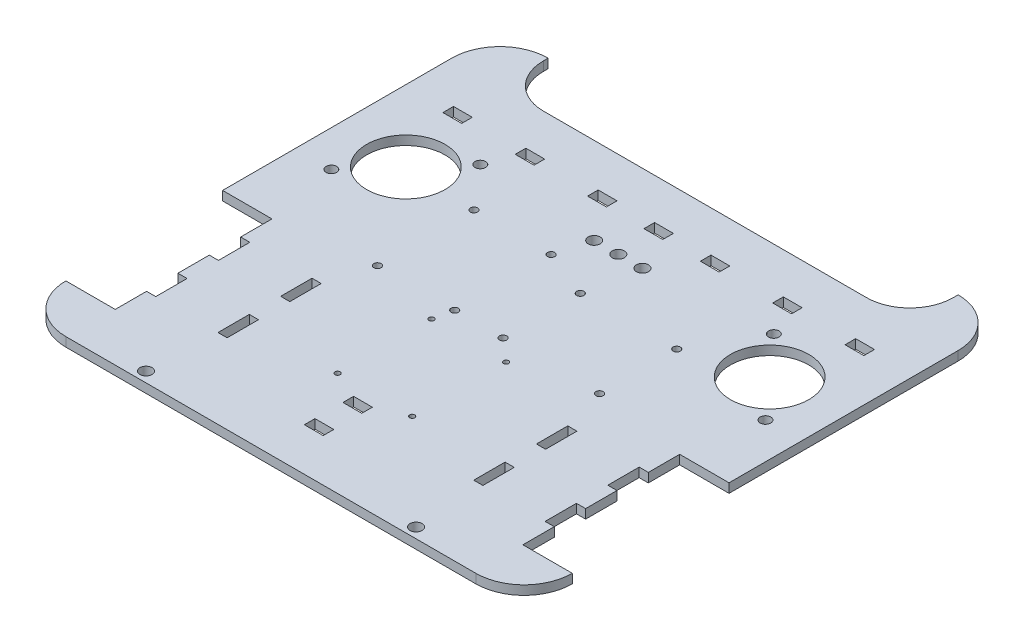
SolidWorks part; units mm, degrees
ref_plane "Front Plane" through (0, 0, 0) normal (0, 0, 1) x (1, 0, 0)
ref_plane "Top Plane" through (0, 0, 0) normal (0, 1, 0) x (1, 0, 0)
ref_plane "Right Plane" through (0, 0, 0) normal (1, 0, 0) x (0, 0, -1)
sketch "Sketch1" plane through (0, 0, 0) normal (0, 1, 0) x (1, 0, 0)
  line L1 (-133.35, 127) -> (133.35, 127)
  line L2 (-133.35, 127) -> (-133.35, -127)
  line L3 (-133.35, -127) -> (133.35, -127)
  line L4 (133.35, 127) -> (133.35, -127)
  line L5 (-133.35, 127) -> (133.35, -127) construction
  line L6 (-133.35, -127) -> (133.35, 127) construction
  point P0 (0, 0)
  dimension "D1" = 266.7
  dimension "D2" = 254
extrude "Boss-Extrude1" add sketch "Sketch1" along normal blind 4.826
sketch "Sketch2" plane through (0, 4.826, 0) normal (0, 1, 0) x (1, 0, 0)
  line L0 (-133.35, 127) -> (-133.35, -127) construction
  line L1 (-133.35, -19.05) -> (-107.35, -19.05)
  line L2 (-133.35, -19.05) -> (-133.35, -101.6)
  line L3 (-133.35, -101.6) -> (-107.35, -101.6)
  line L4 (-107.35, -19.05) -> (-107.35, -101.6)
  line L5 (133.35, -127) -> (133.35, 127) construction
  line L6 (133.35, -19.05) -> (107.35, -19.05)
  line L7 (133.35, -19.05) -> (133.35, -101.6)
  line L8 (133.35, -101.6) -> (107.35, -101.6)
  line L9 (107.35, -19.05) -> (107.35, -101.6)
  line L10 (-133.35, -127) -> (133.35, -127) construction
  dimension "D1" = 25.4
  dimension "D2" = 25.4
  dimension "D3" = 82.55
  dimension "D4" = 82.55
  dimension "D5" = 26
  dimension "D6" = 26
extrude "Cut-Extrude1" cut sketch "Sketch2" against normal blind 4.826
sketch "Sketch4" plane through (0, 4.826, 0) normal (0, 1, 0) x (1, 0, 0)
  line L0 (0, -127) -> (0, 127) construction
  line L1 (-133.35, -127) -> (133.35, -127) construction
  line L2 (133.35, 127) -> (-133.35, 127) construction
  line L3 (-133.35, 101.6) -> (-107.95, 101.6) construction
  line L4 (-133.35, 127) -> (-133.35, -19.05) construction
  line L5 (-107.95, 101.6) -> (-107.95, 127) construction
  line L6 (-133.35, 101.6) -> (-133.35, 127)
  line L7 (-133.35, 127) -> (-107.95, 127)
  line L8 (133.35, 101.6) -> (133.35, 127)
  line L9 (133.35, 127) -> (107.95, 127)
  arc A0 (-133.35, 101.6) -> (-107.95, 127) centre (-107.95, 101.6) cw
  arc A1 (133.35, 101.6) -> (107.95, 127) centre (107.95, 101.6) ccw
extrude "Cut-Extrude3" cut sketch "Sketch4" against normal blind 4.826
sketch "Sketch7" plane through (0, 4.826, 0) normal (0, 1, 0) x (1, 0, 0)
  line L0 (0, -127) -> (0, 127) construction
  line L1 (-133.35, -127) -> (133.35, -127) construction
  line L2 (107.95, 127) -> (-107.95, 127) construction
  line L3 (107.95, 101.6) -> (107.95, 127)
  line L4 (107.95, 101.6) -> (-107.95, 101.6)
  line L5 (0, 101.6) -> (0, 127)
  line L6 (107.95, 127) -> (-107.95, 127)
  line L7 (-107.95, 101.6) -> (-107.95, 127)
  line M6 (107.95, 127) -> (-107.95, 127)
  dimension "D2" = 107.95
extrude "Cut-Extrude5" cut sketch "Sketch7" against normal blind 4.826 contours L7 L4 L5 M6 | L5 L4 L3 M6 region at (53.975, 4.826, -114.3) region at (-53.975, 4.826, -114.3)
fillet "Fillet9" radius 22.86 1 edges at (-107.95, 2.413, -101.6) type face fillet first side face at (0, 2.413, -101.6) second side face at (-107.95, 2.413, -114.3)
fillet "Fillet10" radius 22.86 1 edges at (107.95, 2.413, -101.6) type face fillet first side face at (11.43, 2.413, -101.6) second side face at (107.95, 2.413, -114.3)
sketch "Sketch8" plane through (0, 4.826, 0) normal (0, 1, 0) x (1, 0, 0)
  line L0 (-133.35, -101.6) -> (-107.95, -101.6) construction
  line L1 (-107.95, -101.6) -> (-107.95, -127) construction
  line L2 (-133.35, -127) -> (133.35, -127) construction
  line L3 (-133.35, -101.6) -> (-133.35, -127)
  line L4 (-133.35, -127) -> (-107.95, -127)
  line L5 (0, -127) -> (0, 101.6) construction
  line L6 (85.09, 101.6) -> (-85.09, 101.6) construction
  line L7 (133.35, -127) -> (107.95, -127)
  line L8 (133.35, -101.6) -> (133.35, -127)
  arc A0 (-133.35, -101.6) -> (-107.95, -127) centre (-107.95, -101.6) ccw
  arc A1 (133.35, -101.6) -> (107.95, -127) centre (107.95, -101.6) cw
extrude "Cut-Extrude6" cut sketch "Sketch8" against normal blind 4.826
sketch "Sketch9" plane through (0, 4.826, 0) normal (0, 1, 0) x (1, 0, 0)
  line L0 (0, 0) -> (133.35, 0) construction
  line L1 (133.35, -19.05) -> (133.35, 101.6) construction
  line L2 (0, 0) -> (-133.35, 0) construction
  line L3 (-133.35, 101.6) -> (-133.35, -19.05) construction
  line L4 (0, 101.6) -> (0, -127) construction
  line L5 (85.09, 101.6) -> (-85.09, 101.6) construction
  line L6 (-107.95, -127) -> (107.95, -127) construction
  circle A2 centre (-71.12, -121.629) radius 3.175
  circle A3 centre (71.12, -121.629) radius 3.175
  dimension "D3" = 6.35
  dimension "D6" = 71.12
extrude "Cut-Extrude7" cut sketch "Sketch9" against normal blind 4.826
sketch "Sketch10" plane through (0, 4.826, 0) normal (0, 1, 0) x (1, 0, 0)
  line L0 (-107.35, -101.6) -> (-107.35, -19.05) construction
  line L1 (-107.35, -35.56) -> (-102.524, -35.56)
  line L2 (-107.35, -35.56) -> (-107.35, -52.07)
  line L3 (-107.35, -52.07) -> (-102.524, -52.07)
  line L4 (-102.524, -35.56) -> (-102.524, -52.07)
  line L5 (107.35, -19.05) -> (107.35, -101.6) construction
  line L6 (-107.35, -68.58) -> (-102.524, -68.58)
  line L7 (-107.35, -68.58) -> (-107.35, -85.09)
  line L8 (-107.35, -85.09) -> (-102.524, -85.09)
  line L9 (-102.524, -68.58) -> (-102.524, -85.09)
  line L10 (107.35, -35.56) -> (102.524, -35.56)
  line L11 (107.35, -35.56) -> (107.35, -52.07)
  line L12 (107.35, -52.07) -> (102.524, -52.07)
  line L13 (102.524, -35.56) -> (102.524, -52.07)
  line L14 (-107.35, -19.05) -> (-102.524, -19.05) construction
  line L15 (107.35, -68.58) -> (102.524, -68.58)
  line L16 (107.35, -68.58) -> (107.35, -85.09)
  line L17 (107.35, -85.09) -> (102.524, -85.09)
  line L18 (102.524, -68.58) -> (102.524, -85.09)
  line L19 (-102.524, -19.05) -> (-102.524, -35.56) construction
  line L20 (-102.524, -52.07) -> (-102.524, -68.58) construction
  line L21 (-102.524, -68.58) -> (-83.474, -80.9089) construction
  line L22 (-107.35, -101.6) -> (-102.524, -101.6)
  line L23 (-102.524, -101.6) -> (-102.524, -85.09)
  line L24 (-102.524, -85.09) -> (-83.474, -98.2941)
  line L25 (107.35, -101.6) -> (102.524, -101.6)
  line L26 (102.524, -101.6) -> (102.524, -85.09)
  line L27 (102.524, -68.58) -> (102.524, -52.07)
  line L28 (107.35, -19.05) -> (102.524, -19.05)
  line L29 (102.524, -19.05) -> (102.524, -35.56)
  line M19 (107.35, -101.6) -> (107.35, -19.05)
  line M35 (-107.35, -19.05) -> (-107.35, -101.6)
  dimension "D1" = 4.826
  dimension "D2" = 4.826
extrude "Cut-Extrude8" cut sketch "Sketch10" against normal through all contours L9 L6 L8 M35 | L10 L13 L12 M19 | L15 L18 L17 M19 | L2 L3 L4 L1 region at (-104.937, 4.826, 76.835) region at (104.937, 4.826, 43.815) region at (104.937, 4.826, 76.835)
sketch "Sketch12" plane through (0, 0, 0) normal (0, -1, 0) x (1, 0, 0)
  line L0 (-64.932, 68.58) -> (-64.932, 85.09) construction
  line L1 (-64.932, 68.58) -> (-69.758, 68.58) construction
  line L2 (-69.758, 68.58) -> (-69.758, 85.09) construction
  line L3 (-64.932, 85.09) -> (-69.758, 85.09) construction
  line L4 (-64.932, 52.07) -> (-69.758, 52.07) construction
  line L5 (-64.932, 35.56) -> (-64.932, 52.07) construction
  line L6 (-64.932, 35.56) -> (-69.758, 35.56) construction
  line L7 (-69.758, 35.56) -> (-69.758, 52.07) construction
  line L8 (-64.932, 68.58) -> (-64.932, 85.09)
  line L9 (-64.932, 68.58) -> (-69.758, 68.58)
  line L10 (-69.758, 68.58) -> (-69.758, 85.09)
  line L11 (-64.932, 85.09) -> (-69.758, 85.09)
  line L12 (-64.932, 52.07) -> (-69.758, 52.07)
  line L13 (-64.932, 35.56) -> (-64.932, 52.07)
  line L14 (-64.932, 35.56) -> (-69.758, 35.56)
  line L15 (-69.758, 35.56) -> (-69.758, 52.07)
extrude "Cut-Extrude9" cut sketch "Sketch12" against normal through all
sketch "Sketch13" plane through (0, 4.826, 0) normal (0, 1, 0) x (1, 0, 0)
  line L0 (69.758, -68.58) -> (69.758, -85.09) construction
  line L1 (69.758, -68.58) -> (64.932, -68.58) construction
  line L2 (64.932, -68.58) -> (64.932, -85.09) construction
  line L3 (69.758, -85.09) -> (64.932, -85.09) construction
  line L4 (69.758, -52.07) -> (64.932, -52.07) construction
  line L5 (69.758, -35.56) -> (69.758, -52.07) construction
  line L6 (69.758, -35.56) -> (64.932, -35.56) construction
  line L7 (64.932, -35.56) -> (64.932, -52.07) construction
  line L8 (69.758, -68.58) -> (69.758, -85.09)
  line L9 (69.758, -68.58) -> (64.932, -68.58)
  line L10 (64.932, -68.58) -> (64.932, -85.09)
  line L11 (69.758, -85.09) -> (64.932, -85.09)
  line L12 (69.758, -52.07) -> (64.932, -52.07)
  line L13 (69.758, -35.56) -> (69.758, -52.07)
  line L14 (69.758, -35.56) -> (64.932, -35.56)
  line L15 (64.932, -35.56) -> (64.932, -52.07)
extrude "Cut-Extrude10" cut sketch "Sketch13" against normal through all
sketch "Sketch14" plane through (0, 4.826, 0) normal (0, 1, 0) x (1, 0, 0)
  line L0 (-133.35, -19.05) -> (133.35, -19.05) construction
  line L1 (0, -19.05) -> (0, -127) construction
  line L2 (-107.95, -127) -> (107.95, -127) construction
  line L3 (-22.86, -19.05) -> (-22.86, -127) construction
  line L4 (22.86, -19.05) -> (22.86, -127) construction
  dimension "D1" = 22.86
sketch "Sketch15" plane through (0, 4.826, 0) normal (0, 1, 0) x (1, 0, 0)
  circle A0 centre (19.5961, -22.7308) radius 1.3462 construction
  circle A1 centre (-19.6723, -22.7308) radius 1.3462 construction
  circle A2 centre (-19.6723, -72.1636) radius 1.3462 construction
  circle A3 centre (19.5961, -72.1636) radius 1.3462 construction
  circle A4 centre (19.5961, -22.7308) radius 1.3462
  circle A5 centre (-19.6723, -22.7308) radius 1.3462
  circle A6 centre (-19.6723, -72.1636) radius 1.3462
  circle A7 centre (19.5961, -72.1636) radius 1.3462
extrude "Cut-Extrude11" cut sketch "Sketch15" against normal through all
sketch "Sketch16" plane through (0, 4.826, 0) normal (0, 1, 0) x (1, 0, 0)
  line L0 (0, 101.6) -> (0, -127) construction
  line L1 (85.09, 101.6) -> (-85.09, 101.6) construction
  circle A0 centre (77.2939, 60.6102) radius 2.7781 construction
  circle A1 centre (114.3, 19.1646) radius 2.7781 construction
  circle A2 centre (95.7969, 39.8874) radius 20.6375 construction
  circle A3 centre (77.2939, 60.6102) radius 2.7781
  circle A4 centre (114.3, 19.1646) radius 2.7781
  circle A5 centre (95.7969, 39.8874) radius 20.6375
  circle A6 centre (-95.7969, 39.8874) radius 20.6375
  circle A7 centre (-77.2939, 60.6102) radius 2.7781
  circle A8 centre (-114.3, 19.1646) radius 2.7781
extrude "Cut-Extrude12" cut sketch "Sketch16" against normal through all
sketch "Sketch17" plane through (0, 4.826, 0) normal (0, 1, 0) x (1, 0, 0)
  line L0 (-62.8429, 80.0388) -> (-62.8429, 74.4508)
  line L1 (-110.8489, 80.0388) -> (-100.9429, 80.0388)
  line L2 (-110.8489, 80.0388) -> (-110.8489, 74.4508)
  line L3 (-110.8489, 74.4508) -> (-100.9429, 74.4508)
  line L4 (-100.9429, 80.0388) -> (-100.9429, 74.4508)
  line L9 (-72.7489, 80.0388) -> (-62.8429, 80.0388)
  line L10 (-72.7489, 80.0388) -> (-72.7489, 74.4508)
  line L11 (-72.7489, 74.4508) -> (-62.8429, 74.4508)
  line L12 (-24.7429, 80.0388) -> (-24.7429, 74.4508)
  line L13 (-34.6489, 80.0388) -> (-24.7429, 80.0388)
  line L14 (-34.6489, 80.0388) -> (-34.6489, 74.4508)
  line L15 (-34.6489, 74.4508) -> (-24.7429, 74.4508)
  line L16 (-133.35, 101.6) -> (-133.35, -19.05) construction
  line L17 (0, 101.6) -> (0, -127)
  line L18 (85.09, 101.6) -> (-85.09, 101.6) construction
  line L19 (-100.9429, 74.4508) -> (-78.3377, 74.4508) construction
  line L20 (24.7429, 80.0388) -> (24.7429, 74.4508)
  line L21 (34.6489, 80.0388) -> (24.7429, 80.0388)
  line L22 (34.6489, 80.0388) -> (34.6489, 74.4508)
  line L23 (34.6489, 74.4508) -> (24.7429, 74.4508)
  line L24 (62.8429, 80.0388) -> (62.8429, 74.4508)
  line L25 (72.7489, 74.4508) -> (62.8429, 74.4508)
  line L26 (72.7489, 80.0388) -> (72.7489, 74.4508)
  line L27 (72.7489, 80.0388) -> (62.8429, 80.0388)
  line L28 (110.8489, 80.0388) -> (100.9429, 80.0388)
  line L29 (110.8489, 80.0388) -> (110.8489, 74.4508)
  line L30 (110.8489, 74.4508) -> (100.9429, 74.4508)
  line L31 (100.9429, 80.0388) -> (100.9429, 74.4508)
  line L36 (4.953, 74.4508) -> (4.953, 80.0388)
  line L37 (4.953, 74.4508) -> (-4.953, 74.4508)
  line L38 (4.953, 80.0388) -> (-4.953, 80.0388)
  line L39 (-4.953, 74.4508) -> (-4.953, 80.0388)
  line L40 (4.953, 74.4508) -> (-4.953, 80.0388) construction
  line L41 (4.953, 80.0388) -> (-4.953, 74.4508) construction
  point P42 (0, 77.2448)
  dimension "D1" = 9.906
  dimension "D2" = 5.588
  dimension "D6" = 3
  dimension "D7" = 22.5011
  dimension "D8" = 9.906
  dimension "D9" = 0
extrude "Cut-Extrude13" cut sketch "Sketch17" against normal through all contours L28 L31 L30 L29 | L26 L27 L24 L25 | L23 L22 L21 L20 | L36 L38 L17 L37 | L39 L37 L17 L38 | L14 L15 L12 L13 | L10 L11 L0 L9 | L4 L1 L2 L3 region at (-67.7959, 4.826, -77.2448) region at (-105.8959, 4.826, -77.2448) region at (-29.6959, 4.826, -77.2448) region at (2.4765, 4.826, -77.2448) region at (-2.4765, 4.826, -77.2448) region at (29.6959, 4.826, -77.2448) region at (67.7959, 4.826, -77.2448) region at (105.8959, 4.826, -77.2448)
sketch "Sketch18" plane through (0, 4.826, 0) normal (0, 1, 0) x (1, 0, 0)
  line L0 (-4.953, -104.394) -> (4.953, -104.394)
  line L1 (-4.953, -104.394) -> (-4.953, -98.806)
  line L2 (4.953, -104.394) -> (4.953, -98.806)
  line L3 (-4.953, -98.806) -> (4.953, -98.806)
  line L4 (-4.953, -104.394) -> (4.953, -98.806) construction
  line L5 (4.953, -104.394) -> (-4.953, -98.806) construction
  line L6 (0, -19.05) -> (0, -127) construction
  line L7 (-4.953, -84.074) -> (4.953, -84.074)
  line L8 (-4.953, -84.074) -> (-4.953, -78.486)
  line L9 (4.953, -84.074) -> (4.953, -78.486)
  line L10 (-4.953, -78.486) -> (4.953, -78.486)
  line L11 (-4.953, -84.074) -> (4.953, -78.486) construction
  line L12 (4.953, -84.074) -> (-4.953, -78.486) construction
  point P1 (0, -101.6)
  point P10 (0, -81.28)
  dimension "D1" = 9.906
  dimension "D2" = 5.588
  dimension "D3" = 0
  dimension "D4" = 25.4
  dimension "D5" = 2
extrude "Cut-Extrude14" cut sketch "Sketch18" against normal through all
sketch "Sketch19" plane through (0, 4.826, 0) normal (0, 1, 0) x (1, 0, 0)
  line L0 (4.953, 74.4508) -> (-4.953, 74.4508) construction
  circle A0 centre (0, 55.982) radius 3.175
  circle A1 centre (12.7, 55.982) radius 3.175
  circle A2 centre (-12.7, 55.982) radius 3.175
  point P2 (0, 74.4508)
  point P5 (0, 74.4508)
  point P6 (0, 74.4508)
  dimension "D1" = 6.35
  dimension "D2" = 2
  dimension "D3" = 2
extrude "Cut-Extrude15" cut sketch "Sketch19" against normal through all
sketch "Sketch20" plane through (0, 4.826, 0) normal (0, 1, 0) x (1, 0, 0)
  line L0 (0, -19.05) -> (0, 101.6)
  line L1 (85.09, 101.6) -> (-85.09, 101.6) construction
  circle A0 centre (-58.2439, 38.202) radius 1.905
  circle A1 centre (-17.6039, 38.202) radius 1.905
  circle A2 centre (-58.2439, -12.598) radius 1.905
  circle A3 centre (-17.6039, -12.598) radius 1.905
  circle A4 centre (-12.7, 55.982) radius 3.175 construction
  circle A5 centre (-77.2939, 60.6102) radius 2.7781 construction
  dimension "D1" = 3.81
  dimension "D3" = 3.81
  dimension "D4" = 3.81
  dimension "D6" = 3.81
  dimension "D10" = 19.05
  dimension "D2" = 40.64
  dimension "D5" = 50.8
  dimension "D7" = 40.64
  dimension "D8" = 50.8
  dimension "D9" = 17.78
extrude "Cut-Extrude16" cut sketch "Sketch20" against normal through all contours A1 | A0 | A2 | A3 region at (-58.2439, 4.826, -38.202) region at (-17.6039, 4.826, -38.202) region at (-58.2439, 4.826, 12.598) region at (-17.6039, 4.826, 12.598)
sketch "Sketch21" plane through (0, 4.826, 0) normal (0, 1, 0) x (1, 0, 0)
  circle A0 centre (7.7961, 28.1547) radius 1.905
  circle A1 centre (58.5961, 28.1547) radius 1.905
  circle A2 centre (7.7961, -12.4853) radius 1.905
  circle A3 centre (58.5961, -12.4853) radius 1.905
  circle A4 centre (-17.6039, 38.202) radius 1.905 construction
  point P12 (0, 0)
  dimension "D1" = 3.81
  dimension "D2" = 3.81
  dimension "D4" = 3.81
  dimension "D5" = 3.81
  dimension "D7" = 25.4
  dimension "D3" = 50.8
  dimension "D6" = 40.64
  dimension "D8" = 50.8
  dimension "D9" = 40.64
extrude "Cut-Extrude17" cut sketch "Sketch21" against normal through all
equation "\"MDF\"= 0.19in"
equation "\"GenDiameter\"= 60mm"
equation "\"GenCutDiameter\" = 1.8in"
equation "\"GenCutDistance\" = 1"
equation "\"TowerHeight\" = 6in"
equation "\"TowerFrontBase\" = 3in"
equation "\"FunnelHeight\" = 1in"
equation "\"FunnelAngle\" = 20"
equation "\"TowerSideBase\" = 3in"
equation "\"BaseLength\" = 10in"
equation "\"BaseWidth\" = 10.5in"
equation "\"WheelHoleLength\" = 3.25in"
equation "\"WheelHoleWidth\" = 26mm"
equation "\"DropLength\" = 1in"
equation "\"D1@Sketch1\"=\"BaseWidth\""
equation "\"D2@Sketch1\"=\"BaseLength\""
equation "\"D1@Boss-Extrude1\"=\"MDF\""
equation "\"WheelHoleFromBack\" = 1in"
equation "\"D1@Sketch2\"=\"WheelHoleFromBack\""
equation "\"D2@Sketch2\"=\"WheelHoleFromBack\""
equation "\"D3@Sketch2\"=\"WheelHoleLength\""
equation "\"D4@Sketch2\"=\"WheelHoleLength\""
equation "\"D5@Sketch2\"=\"WheelHoleWidth\""
equation "\"D6@Sketch2\"=\"WheelHoleWidth\""
equation "\"D1@Cut-Extrude1\"=\"MDF\""
equation "\"DropWidth\" = 8.5in"
equation "\"BumperWidth\" = 1in"
equation "\"D1@Sketch4\"=\"BumperWidth\""
equation "\"D2@Sketch4\"=\"WheelHoleFromBack\""
equation "\"D1@Cut-Extrude3\"=\"MDF\""
equation "\"D1@Sketch7\"=\"DropLength\""
equation "\"D2@Sketch7\"=\"DropWidth\"/2"
equation "\"D1@Cut-Extrude5\"=\"MDF\""
equation "\"D1@Sketch8\"=\"BumperWidth\""
equation "\"D1@Cut-Extrude6\"=\"MDF\""
equation "\"HoleDiameter\" = 0.25in"
equation "\"D3@Sketch9\"=\"HoleDiameter\""
equation "\"D1@Cut-Extrude7\"=\"MDF\""
equation "\"D1@Sketch10\"=\"MDF\""
equation "\"D2@Sketch10\"=\"MDF\""
